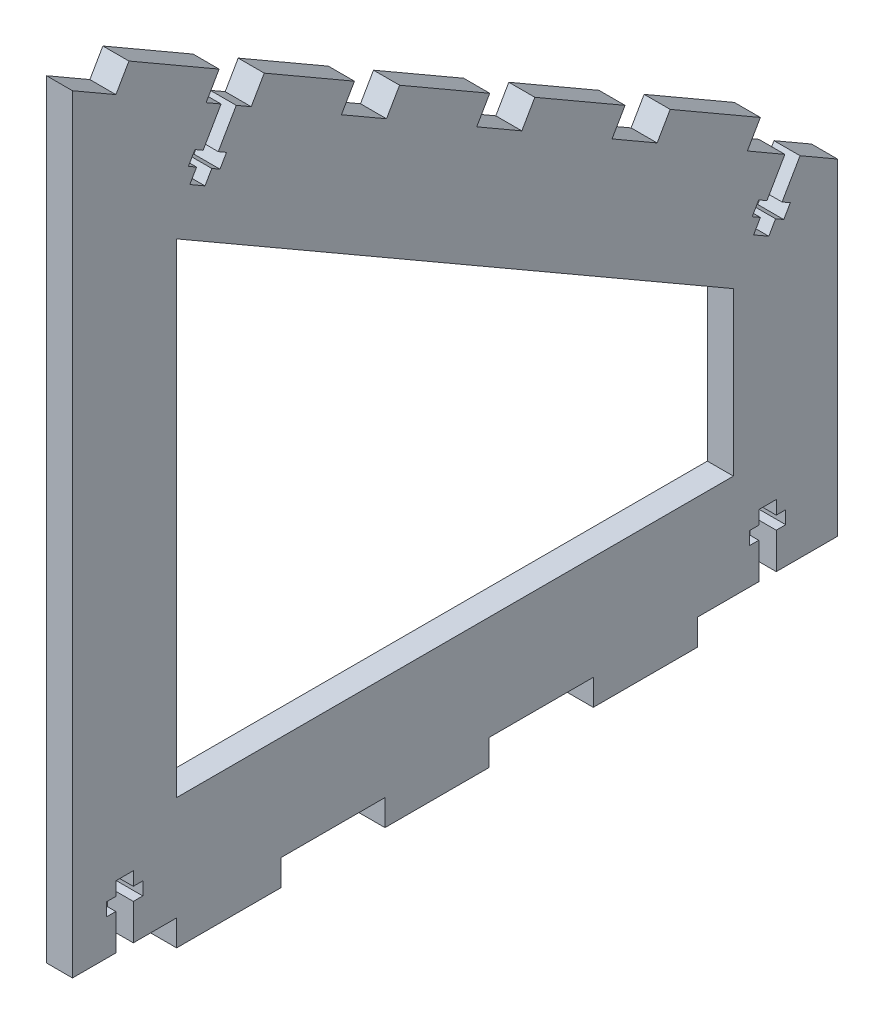
SolidWorks part; units mm, degrees
ref_plane "Front Plane" through (0, 0, 0) normal (0, 0, 1) x (1, 0, 0)
ref_plane "Top Plane" through (0, 0, 0) normal (0, 1, 0) x (1, 0, 0)
ref_plane "Right Plane" through (0, 0, 0) normal (1, 0, 0) x (0, 0, -1)
sketch "Sketch1" plane through (-32.0384, 0, 0) normal (-1, 0, 0) x (0, 0, 1)
  line L0 (-215.9, 95.25) -> (-215.9, 174.9125)
  line L1 (165.3114, 95.25) -> (152.9655, 95.25) construction
  line L2 (-215.9, 174.9125) -> (-29.3333, 282.6268)
  line L3 (-29.3333, 282.6268) -> (-29.3333, 95.25)
  line L4 (-29.3333, 95.25) -> (-215.9, 95.25)
  line L5 (-29.3333, 282.6268) -> (-53.9437, 268.418) construction
  line L6 (-29.3333, 95.25) -> (-29.3333, 282.6268) construction
extrude "Boss-Extrude1" add sketch "Sketch1" along normal mid plane 6.35
sketch "Sketch2" plane through (-35.2134, 0, 0) normal (-1, 0, 0) x (0, 0, 1)
  line L4 (-190.5, 160.2478) -> (-190.5, 120.65)
  line L5 (-190.5, 160.2478) -> (-190.5, 120.65)
  line L14 (-54.7333, 120.65) -> (-54.7333, 238.6327)
  line L15 (-190.5, 120.65) -> (-54.7333, 120.65)
  line L16 (-54.7333, 238.6327) -> (-190.5, 160.2478)
  line L17 (-54.7333, 120.65) -> (-54.7333, 238.6327)
  line L18 (-190.5, 120.65) -> (-54.7333, 120.65)
  line L19 (-54.7333, 238.6327) -> (-190.5, 160.2478)
  dimension "D1" = 25.4
extrude "Cut-Extrude1" cut sketch "Sketch2" against normal blind 6.35
sketch "Sketch3" plane through (0, 224.6718, -129.7143) normal (0, 0.866, -0.5) x (1, 0, 0)
  line L0 (-35.2134, -115.91) -> (-35.2134, 99.5186) construction
  line L1 (-35.2134, 74.1186) -> (-28.8634, 74.1186)
  line L2 (-35.2134, 74.1186) -> (-35.2134, 48.7186)
  line L3 (-35.2134, 48.7186) -> (-28.8634, 48.7186)
  line L4 (-28.8634, 74.1186) -> (-28.8634, 48.7186)
  line L5 (-28.8634, -115.91) -> (-28.8634, 99.5186) construction
  dimension "D1" = 25.4
  dimension "D2" = 25.4
extrude "Boss-Extrude2" add sketch "Sketch3" along normal blind 6.35
pattern_linear "LPattern1" count 5 spacing 38.1 along (0, 0.5, 0.866) of "Boss-Extrude2"
sketch "Sketch4" plane through (0, 95.25, 0) normal (0, -1, 0) x (1, 0, 0)
  line L0 (-35.2134, -215.9) -> (-35.2134, -29.3333) construction
  line L1 (-35.2134, -54.7333) -> (-28.8634, -54.7333)
  line L2 (-35.2134, -54.7333) -> (-35.2134, -80.1333)
  line L3 (-35.2134, -80.1333) -> (-28.8634, -80.1333)
  line L4 (-28.8634, -54.7333) -> (-28.8634, -80.1333)
  line L5 (-28.8634, -215.9) -> (-28.8634, -29.3333) construction
  dimension "D1" = 25.4
  dimension "D2" = 25.4
extrude "Boss-Extrude3" add sketch "Sketch4" along normal blind 6.35
pattern_linear "LPattern2" count 3 spacing 50.8 along (0, 0, -1) of "Boss-Extrude3"
sketch "Sketch5" plane through (-28.8634, 0, 0) normal (1, 0, 0) x (0, 0, -1)
  line L0 (-152.9655, 95.25) -> (-165.3114, 95.25) construction
  line L1 (198.8167, 95.25) -> (198.8167, 119.6237) construction
  line L2 (215.9, 95.25) -> (181.7333, 95.25) construction
  line L3 (42.0333, 95.25) -> (42.0333, 127.2639) construction
  line L4 (54.7333, 95.25) -> (29.3333, 95.25) construction
  line L5 (-152.9655, 95.25) -> (-165.3114, 95.25) construction
  line B0 (196.6831, 95.25) -> (200.9503, 95.25)
  line B1 (200.9503, 107.188) -> (203.2617, 107.188)
  line B2 (203.2617, 107.188) -> (203.2617, 104.013)
  line B3 (203.2617, 104.013) -> (200.9503, 104.013)
  line B4 (200.9503, 104.013) -> (200.9503, 95.25)
  line B5 (200.9503, 107.188) -> (200.9503, 110.49)
  line B6 (200.9503, 110.49) -> (196.6831, 110.49)
  line B7 (196.6831, 107.188) -> (196.6831, 110.49)
  line B8 (196.6831, 104.013) -> (196.6831, 95.25)
  line B9 (194.3717, 104.013) -> (196.6831, 104.013)
  line B10 (194.3717, 107.188) -> (194.3717, 104.013)
  line B11 (196.6831, 107.188) -> (194.3717, 107.188)
  line B12 (39.8997, 95.25) -> (44.1669, 95.25)
  line B13 (44.1669, 107.188) -> (46.4783, 107.188)
  line B14 (46.4783, 107.188) -> (46.4783, 104.013)
  line B15 (46.4783, 104.013) -> (44.1669, 104.013)
  line B16 (44.1669, 104.013) -> (44.1669, 95.25)
  line B17 (44.1669, 107.188) -> (44.1669, 110.49)
  line B18 (44.1669, 110.49) -> (39.8997, 110.49)
  line B19 (39.8997, 107.188) -> (39.8997, 110.49)
  line B20 (39.8997, 104.013) -> (39.8997, 95.25)
  line B21 (37.5883, 104.013) -> (39.8997, 104.013)
  line B22 (37.5883, 107.188) -> (37.5883, 104.013)
  line B23 (39.8997, 107.188) -> (37.5883, 107.188)
sketch_block_instance "TSlot-1"
sketch_block "TSlot" parameters "D1"=3.302, "D2"=3.175
sketch_block_instance "TSlot-3"
extrude "Cut-Extrude2" cut sketch "Sketch5" against normal blind 6.35
sketch "Sketch6" plane through (-28.8634, 0, 0) normal (1, 0, 0) x (0, 0, -1)
  line L1 (51.3304, 269.9268) -> (73.3274, 257.2268) construction
  line L3 (183.3127, 193.7268) -> (205.3097, 181.0268) construction
  line L4 (204.9015, 181.2625) -> (174.0343, 127.799) construction
  line L5 (193.903, 187.6125) -> (215.9, 174.9125) construction
  line L6 (67.4199, 260.6375) -> (38.3031, 210.2056) construction
  line L7 (61.9207, 263.8125) -> (72.9192, 257.4625) construction
  line B0 (206.7492, 180.1957) -> (203.0537, 182.3293)
  line B1 (197.0847, 171.9907) -> (195.083, 173.1464)
  line B2 (195.083, 173.1464) -> (196.6705, 175.896)
  line B3 (196.6705, 175.896) -> (198.6722, 174.7403)
  line B4 (198.6722, 174.7403) -> (203.0537, 182.3293)
  line B5 (197.0847, 171.9907) -> (195.4337, 169.1311)
  line B6 (195.4337, 169.1311) -> (199.1292, 166.9975)
  line B7 (200.7802, 169.8571) -> (199.1292, 166.9975)
  line B8 (202.3677, 172.6067) -> (206.7492, 180.1957)
  line B9 (204.3695, 171.451) -> (202.3677, 172.6067)
  line B10 (202.782, 168.7014) -> (204.3695, 171.451)
  line B11 (200.7802, 169.8571) -> (202.782, 168.7014)
  line B12 (69.2677, 259.5707) -> (65.5722, 261.7043)
  line B13 (59.6032, 251.3657) -> (57.6015, 252.5214)
  line B14 (57.6015, 252.5214) -> (59.189, 255.271)
  line B15 (59.189, 255.271) -> (61.1907, 254.1153)
  line B16 (61.1907, 254.1153) -> (65.5722, 261.7043)
  line B17 (59.6032, 251.3657) -> (57.9522, 248.5061)
  line B18 (57.9522, 248.5061) -> (61.6477, 246.3725)
  line B19 (63.2987, 249.2321) -> (61.6477, 246.3725)
  line B20 (64.8862, 251.9817) -> (69.2677, 259.5707)
  line B21 (66.8879, 250.826) -> (64.8862, 251.9817)
  line B22 (65.3004, 248.0764) -> (66.8879, 250.826)
  line B23 (63.2987, 249.2321) -> (65.3004, 248.0764)
sketch_block_instance "TSlot-4"
sketch_block_instance "TSlot-5"
extrude "Cut-Extrude3" cut sketch "Sketch6" against normal blind 6.35
